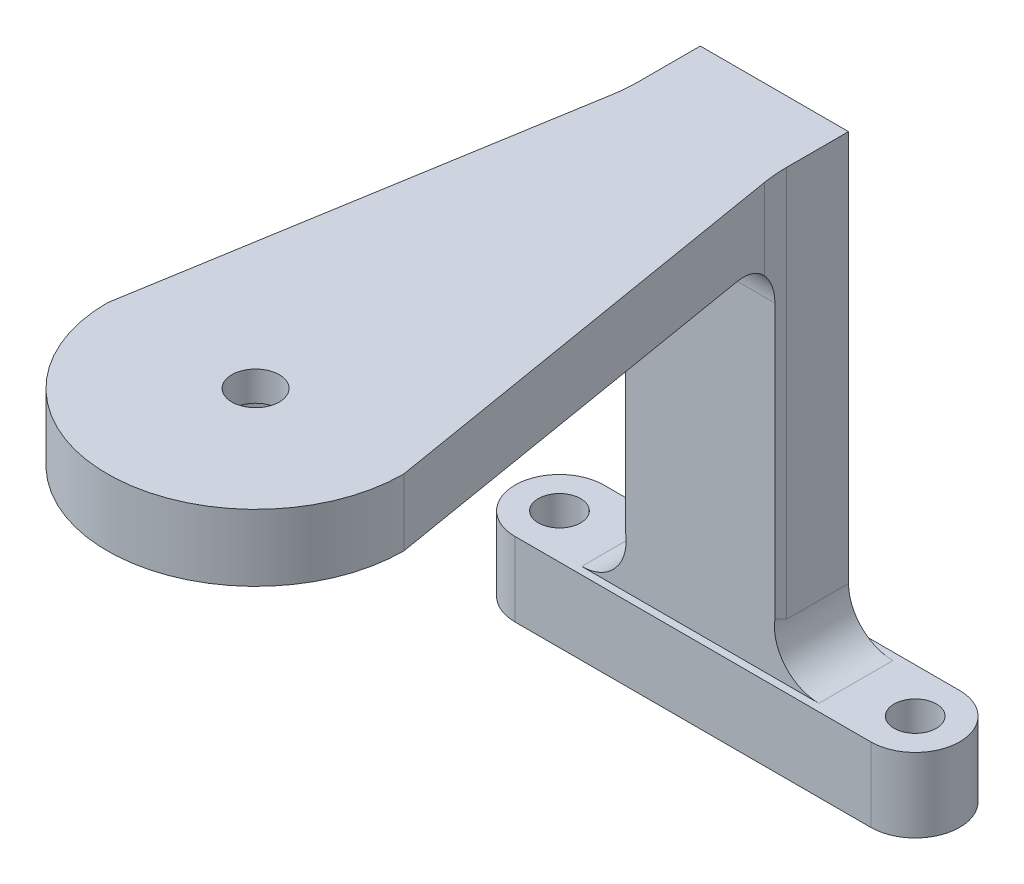
SolidWorks part; units mm, degrees
ref_plane "Front Plane" through (0, 0, 0) normal (0, 0, 1) x (1, 0, 0)
ref_plane "Top Plane" through (0, 0, 0) normal (0, 1, 0) x (1, 0, 0)
ref_plane "Right Plane" through (0, 0, 0) normal (1, 0, 0) x (0, 0, -1)
sketch "Sketch3" plane through (0, 0, 0) normal (0, 1, 0) x (1, 0, 0)
  line L2 (0, 0) -> (0, 30)
  line L3 (0, 30) -> (20, 30)
  line L4 (20, 0) -> (20, 30)
  circle A0 centre (10, 0) radius 3
  arc A1 (0, 0) -> (20, 0) centre (10, 0) ccw
  point P9 (10, 30)
  dimension "D3" = 6
  dimension "D1" = 30
  dimension "D2" = 20
extrude "Boss-Extrude3" add sketch "Sketch3" along normal blind 2.5
sketch "Sketch4" plane through (0, 2.5, 0) normal (0, 1, 0) x (1, 0, 0)
  line L3 (20, 0) -> (20, 30)
  line L4 (20, 30) -> (0, 30)
  line L5 (0, 30) -> (0, 0)
  line L6 (20, 0) -> (20, 30)
  line L8 (0, 30) -> (0, 0)
  line L10 (20, 30) -> (0, 30)
  circle A0 centre (10, 0) radius 1.6
  arc A1 (0, 0) -> (20, 0) centre (10, 0) ccw
  arc A2 (0, 0) -> (20, 0) centre (10, 0) ccw
  dimension "D2" = 3.2
  dimension "D1" = 0
extrude "Boss-Extrude4" add sketch "Sketch4" along normal blind 2
sketch "Sketch5" plane through (0, 0, -30) normal (0, 0, -1) x (-1, 0, 0)
  line L1 (-15, 4.5) -> (-5, 4.5)
  line L2 (-15, 4.5) -> (-15, -24.9)
  line L3 (-15, -24.9) -> (-5, -24.9)
  line L4 (-5, 4.5) -> (-5, -24.9)
  line L5 (-20, 4.5) -> (0, 4.5) construction
  point P4 (0, 0)
  point P5 (0, 0)
  point P8 (0, 0)
  point P10 (-10, 4.5)
  point P11 (-10, 4.5)
  dimension "D1" = 29.4
  dimension "D2" = 10
extrude "Boss-Extrude5" add sketch "Sketch5" along normal blind 5
ref_plane "Plane2" through (15, 4.5, -30) normal (0, -1, 0) x (-1, 0, 0)
sketch "Sketch10" plane through (0, -24.9, 0) normal (0, -1, 0) x (1, 0, 0)
  line L0 (-2, -32.5) -> (22, -32.5) construction
  line L5 (15, -30) -> (5, -30) construction
  line L6 (15, -35) -> (15, -30) construction
  line L7 (15, -35) -> (15, -30) construction
  line L8 (22, -29.5) -> (-2, -29.5)
  line L9 (22, -35.5) -> (-2, -35.5)
  arc A0 (22, -35.5) -> (22, -29.5) centre (22, -32.5) ccw
  arc A1 (-2, -29.5) -> (-2, -35.5) centre (-2, -32.5) ccw
  circle A2 centre (-2, -32.5) radius 1.425
  circle A3 centre (22, -32.5) radius 1.425
  point P4 (10, -30)
  point P5 (10, -32.5)
  point P8 (15, -32.5)
  dimension "D1" = 6
  dimension "D3" = 2.85
  dimension "D2" = 7
extrude "Boss-Extrude8" add sketch "Sketch10" along normal blind 5
sketch "Sketch11" plane through (0, 4.5, 0) normal (0, 1, 0) x (1, 0, 0)
  line L0 (5, 30) -> (0, 0)
  line L1 (15, 30) -> (20, 0)
  line L2 (20, 0) -> (20, 30)
  line L3 (20, 30) -> (15, 30)
  line L4 (5, 30) -> (0, 30)
  line L5 (5, 30) -> (0, 30) construction
  line L6 (0, 30) -> (0, 0)
extrude "Cut-Extrude1" cut sketch "Sketch11" against normal blind 5
fillet "Fillet1" radius 3 2 edges at (15, -24.9, -32.5) (5, -24.9, -32.5)
fillet "Fillet2" radius 3 1 edges at (10, 0, -30)
fillet "Fillet3" radius 10 2 edges at (15, 0.75, -30) (5, 0.75, -30)
